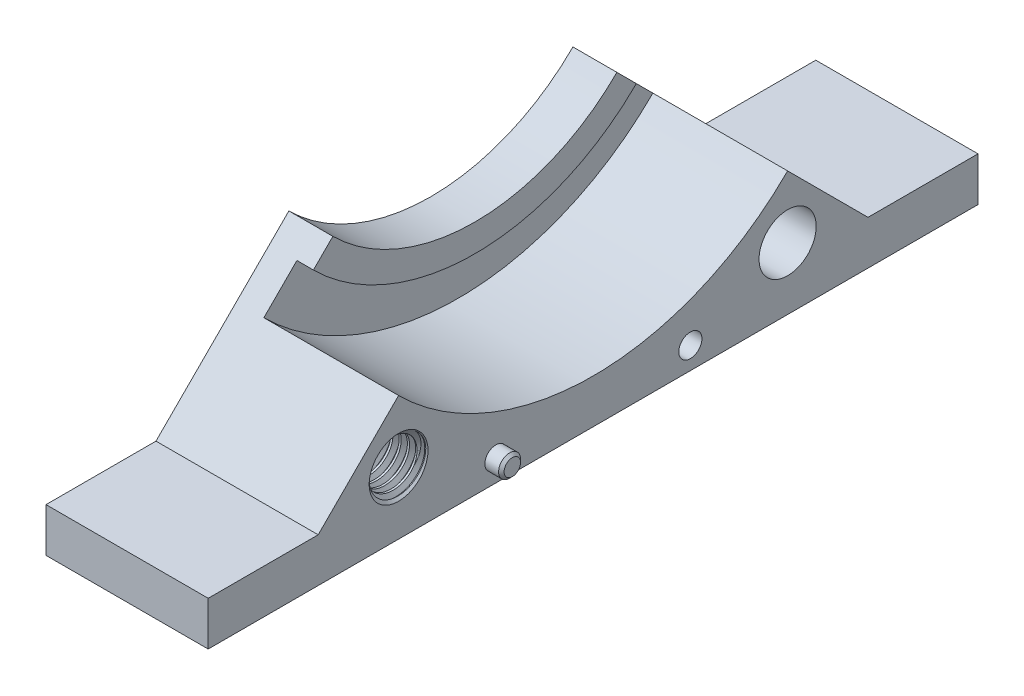
SolidWorks part; units mm, degrees
material "PET"
ref_plane "Front Plane" through (0, 0, 0) normal (0, 0, 1) x (1, 0, 0)
ref_plane "Top Plane" through (0, 0, 0) normal (0, 1, 0) x (1, 0, 0)
ref_plane "Right Plane" through (0, 0, 0) normal (1, 0, 0) x (0, 0, -1)
sketch "Sketch1" plane through (0, 0, 0) normal (1, 0, 0) x (0, 0, -1)
  line L3 (-87.5883, -67.5454) -> (52.4117, -67.5454)
  line L6 (32.4117, -59.5454) -> (52.4117, -59.5454)
  line L7 (52.4117, -59.5454) -> (52.4117, -67.5454)
  line L8 (-67.5883, -59.5454) -> (-43.4183, -35.3755)
  line L9 (-67.5883, -59.5454) -> (-87.5883, -59.5454)
  line L10 (-87.5883, -59.5454) -> (-87.5883, -67.5454)
  line L11 (8.2418, -35.3755) -> (32.4117, -59.5454)
  arc A0 (-52.9643, -44.9215) -> (17.7877, -44.9215) centre (-17.5883, -9.4454) ccw
  arc A1 (-46.9539, -38.911) -> (11.7773, -38.911) centre (-17.5883, -9.4454) ccw
  arc A2 (-43.4183, -35.3755) -> (8.2418, -35.3755) centre (-17.5883, -9.4454) ccw
  dimension "D3" = 100.2
  dimension "D7" = 8.5
  dimension "D8" = 5
  dimension "D1" = 8
  dimension "D2" = 20
  dimension "D4" = 70
  dimension "D5" = 58.1
  dimension "D6" = 70
  dimension "D9" = 135
  dimension "D10" = 135
extrude "Boss-Extrude2" add sketch "Sketch1" along normal blind 29.5 contours A0 L9 L10 L3 L7 L6 region at (0, -60.7953, 17.5883)
extrude "Boss-Extrude3" add sketch "Sketch1<3>" along normal blind 5 contours A1 L8 A0 L11 region at (0, -42.4374, 49.4379)
sketch "Sketch1<3>" plane through (0, 0, 0) normal (1, 0, 0) x (0, 0, -1) same geometry as "Sketch1"
extrude "Boss-Extrude4" add sketch "Sketch1<4>" along normal blind 8 contours A2 L8 A1 L11 region at (0, -37.5731, 44.7563)
sketch "Sketch1<4>" plane through (0, 0, 0) normal (1, 0, 0) x (0, 0, -1) same geometry as "Sketch1"
sketch "Sketch2" plane through (29.5, 0, 0) normal (1, 0, 0) x (0, 0, -1)
  line L0 (-52.9643, -44.9215) -> (-52.9643, -67.5454) construction
  line L1 (-87.5883, -67.5454) -> (52.4117, -67.5454) construction
  line L2 (17.7877, -44.9215) -> (17.7877, -67.5454) construction
  line L3 (-17.5883, -67.5454) -> (-17.5883, -59.5454) construction
  line L4 (-17.5883, -63.5454) -> (-52.9643, -63.5454) construction
  line L5 (-17.5883, -63.5454) -> (17.7877, -63.5454) construction
  circle A0 centre (-52.9643, -56.2335) radius 4.35
  circle A1 centre (17.7877, -56.2335) radius 5.2
  arc A2 (-52.9643, -44.9215) -> (17.7877, -44.9215) centre (-17.5883, -9.4454) ccw construction
  circle A3 centre (-35.2763, -63.5454) radius 2
  circle A4 centre (0.0997, -63.5454) radius 2.1
  point P10 (17.7877, -56.2335)
extrude "Cut-Extrude1" cut sketch "Sketch2" against normal blind 20 contours A1 | A0 region at (29.5, -56.2335, 52.9643) region at (29.5, -56.2335, -17.7877)
extrude "Cut-Extrude2" cut sketch "Sketch2<2>" against normal through all contours A1
sketch "Sketch2<2>" plane through (29.5, 0, 0) normal (1, 0, 0) x (0, 0, -1) same geometry as "Sketch2"
extrude "Boss-Extrude5" add sketch "Sketch2<3>" along normal blind 3 separate body contours A3
sketch "Sketch2<3>" plane through (29.5, 0, 0) normal (1, 0, 0) x (0, 0, -1) same geometry as "Sketch2"
extrude "Cut-Extrude9" cut sketch "Sketch2<5>" against normal blind 4 contours A4 region at (29.5, -63.5454, -0.0997)
sketch "Sketch2<5>" plane through (29.5, 0, 0) normal (1, 0, 0) x (0, 0, -1) same geometry as "Sketch2"
chamfer "Chamfer1" distance 0.5 angle 45 1 edges at (32.5, -63.5454, 33.2763)
chamfer "Chamfer2" distance 1 angle 45 1 edges at (29.5, -56.2335, 48.6143)
thread "Thread3" pitch 1.5 method cut profile "Thread Profile3" start angle 0, offset 2, length 26, pitch 1.5, diameter 8.7
ref_plane "Plane3" through (30.5, -56.2335, 57.3143) normal (0, -1, 0) x (0, 0, 1)
sketch "Thread Profile3" plane through (30.5, -56.2335, 57.3143) normal (0, -1, 0) x (0, 0, 1)
  line L0 (0, 0) -> (0, 1.5) construction
  line L1 (0, 0) -> (0.8119, 0.4687)
  line L2 (0.8119, 0.4687) -> (0.8119, 0.6562)
  line L3 (0.8119, 0.6562) -> (0, 1.125)
  line L4 (0.8119, 0.5625) -> (0, 0.5625) construction
  line L11 (0, 0) -> (0, 1.125)
  point P2 (0, 0)
  dimension "Pitch" = 1.5
  dimension "Profile_Angle" = 60
  dimension "Profile_Land" = 0.1875
  dimension "Profile_Height" = 0.8119
